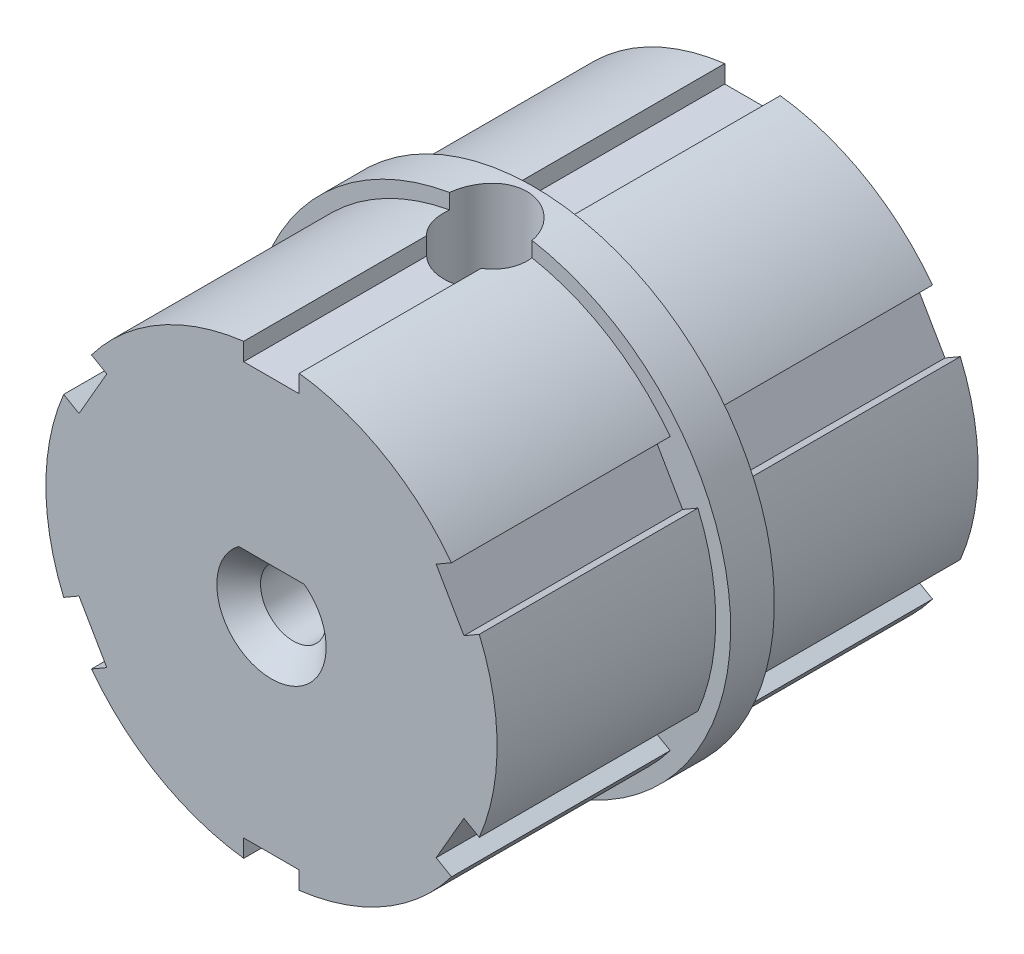
SolidWorks part; units mm, degrees
ref_plane "Спереди" through (0, 0, 0) normal (0, 0, 1) x (1, 0, 0)
ref_plane "Сверху" through (0, 0, 0) normal (0, 1, 0) x (1, 0, 0)
ref_plane "Справа" through (0, 0, 0) normal (1, 0, 0) x (0, 0, -1)
sketch "Эскиз1" plane through (0, 0, 0) normal (0, 0, 1) x (1, 0, 0)
  line L19 (13.2013, -7.8554) -> (13.9033, -8.2607)
  line L20 (13.9033, -0.2201) -> (13.2013, -0.6254)
  line L21 (13.2013, -0.6254) -> (11.9313, 1.5743)
  line L22 (11.9313, 1.5743) -> (12.6333, 1.9796)
  line L23 (5.6699, 5.9999) -> (5.6699, 5.1893)
  line L24 (5.6699, 5.1893) -> (3.1299, 5.1893)
  line L25 (3.1299, 5.1893) -> (3.1299, 5.9999)
  line L26 (-3.8335, 1.9796) -> (-3.1315, 1.5743)
  line L27 (-3.1315, 1.5743) -> (-4.4015, -0.6254)
  line L28 (-4.4015, -0.6254) -> (-5.1035, -0.2201)
  line L29 (-5.1035, -8.2607) -> (-4.4015, -7.8554)
  line L30 (-4.4015, -7.8554) -> (-3.1315, -10.0551)
  line L31 (-3.1315, -10.0551) -> (-3.8335, -10.4604)
  line L32 (3.1299, -14.4807) -> (3.1299, -13.6702)
  line L33 (3.1299, -13.6702) -> (5.6699, -13.6702)
  line L34 (5.6699, -13.6702) -> (5.6699, -14.4807)
  line L35 (12.6333, -10.4604) -> (11.9313, -10.0551)
  line L36 (11.9313, -10.0551) -> (13.2013, -7.8554)
  line L37 (3.2819, -3.2404) -> (5.5179, -3.2404)
  arc A7 (13.9033, -8.2607) -> (13.9033, -0.2201) centre (4.3999, -4.2404) ccw
  arc A8 (12.6333, 1.9796) -> (5.6699, 5.9999) centre (4.3999, -4.2404) ccw
  arc A9 (3.1299, 5.9999) -> (-3.8335, 1.9796) centre (4.3999, -4.2404) ccw
  arc A10 (-5.1035, -0.2201) -> (-5.1035, -8.2607) centre (4.3999, -4.2404) ccw
  arc A11 (-3.8335, -10.4604) -> (3.1299, -14.4807) centre (4.3999, -4.2404) ccw
  arc A12 (5.6699, -14.4807) -> (12.6333, -10.4604) centre (4.3999, -4.2404) ccw
  arc A13 (3.2819, -3.2404) -> (5.5179, -3.2404) centre (4.3999, -4.2404) ccw
  point P31 (4.3999, -2.7404)
  dimension "D1" = 0.5
extrude "Бобышка-Вытянуть1" add sketch "Эскиз1" along normal blind 22
sketch "Эскиз2" plane through (0, 0, 0) normal (0, 0, -1) x (-1, 0, 0)
  circle A3 centre (-4.3999, -4.2404) radius 7.5
extrude "Вырез-Вытянуть1" cut sketch "Эскиз2" against normal blind 9
sketch "Эскиз4" plane through (0, 5.1893, 0) normal (0, 1, 0) x (1, 0, 0)
  line L0 (3.1299, -15.4991) -> (5.6699, -15.4991) construction
  line L1 (4.4287, -15.4991) -> (4.4287, -8.9983) construction
  line L4 (3.1299, -22) -> (3.1299, 0) construction
  line L6 (5.6699, -22) -> (5.6699, 0) construction
  circle A0 centre (4.4287, -12.2487) radius 1.9
  point P0 (4.4287, -15.4991)
  dimension "D1" = 3.8
extrude "Вырез-Вытянуть3" cut sketch "Эскиз4" against normal up to surface (8.4298 mm away) and the other way blind 1 contours A0 up to face at (4.3999, -3.2404, 15.5)
chamfer "Фаска1" distance 1 angle 45 4 edges at (4.3999, -5.7404, 22) (4.3999, -3.2404, 22) (4.3999, -3.2404, 9) (4.3999, -5.7404, 9)
sketch "Эскиз5" plane through (0, 0, 0) normal (0, 0, -1) x (-1, 0, 0)
  circle A0 centre (-4.3999, -4.2404) radius 11
  circle A1 centre (-4.3999, -4.2404) radius 9.4297
extrude "Бобышка-Вытянуть2" add sketch "Эскиз5" against normal blind 2 from offset 10 offset against normal yes
sketch "Эскиз6" plane through (0, 5.1893, 0) normal (0, 1, 0) x (1, 0, 0)
  circle A0 centre (4.4287, -12.2487) radius 1.9
extrude "Вырез-Вытянуть4" cut sketch "Эскиз6" against normal blind 2 and the other way blind 2
